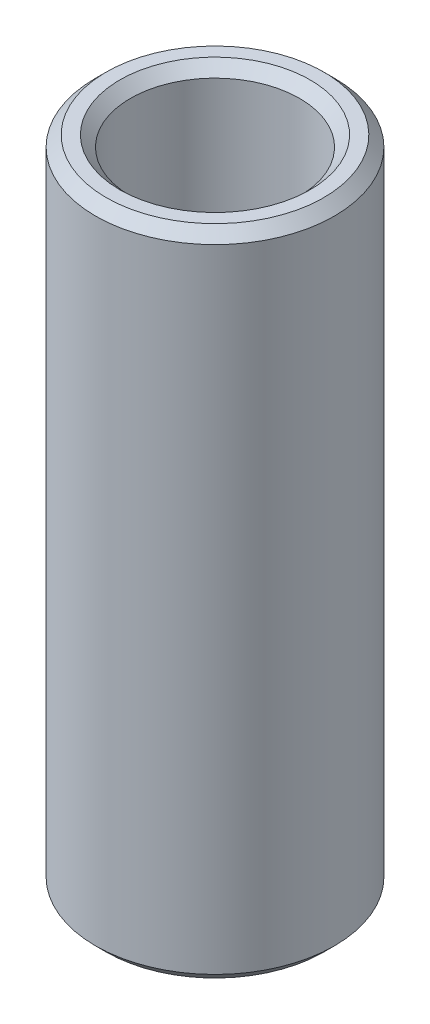
SolidWorks part; units mm, degrees
ref_plane "Front Plane" through (0, 0, 0) normal (0, 0, 1) x (1, 0, 0)
ref_plane "Top Plane" through (0, 0, 0) normal (0, 1, 0) x (1, 0, 0)
ref_plane "Right Plane" through (0, 0, 0) normal (1, 0, 0) x (0, 0, -1)
sketch "Sketch1" plane through (0, 0, 0) normal (0, 1, 0) x (1, 0, 0)
  circle A0 centre (0, 0) radius 15
  dimension "SLEEVE_OD" = 30
extrude "Boss-Extrude1" add sketch "Sketch1" along normal blind 82.0456
sketch "Sketch2" plane through (0, 0, 0) normal (0, 1, 0) x (1, 0, 0)
  circle A0 centre (0, 0) radius 10.6181
  dimension "BORE_D" = 21.2361
extrude "Cut-Extrude1" cut sketch "Sketch2" along normal through all
chamfer "Chamfer1" distance 1.3371 angle 45 4 edges at (0, 82.0456, 10.6181) (0, 0, 10.6181) (0, 0, 15) (0, 82.0456, 15)
